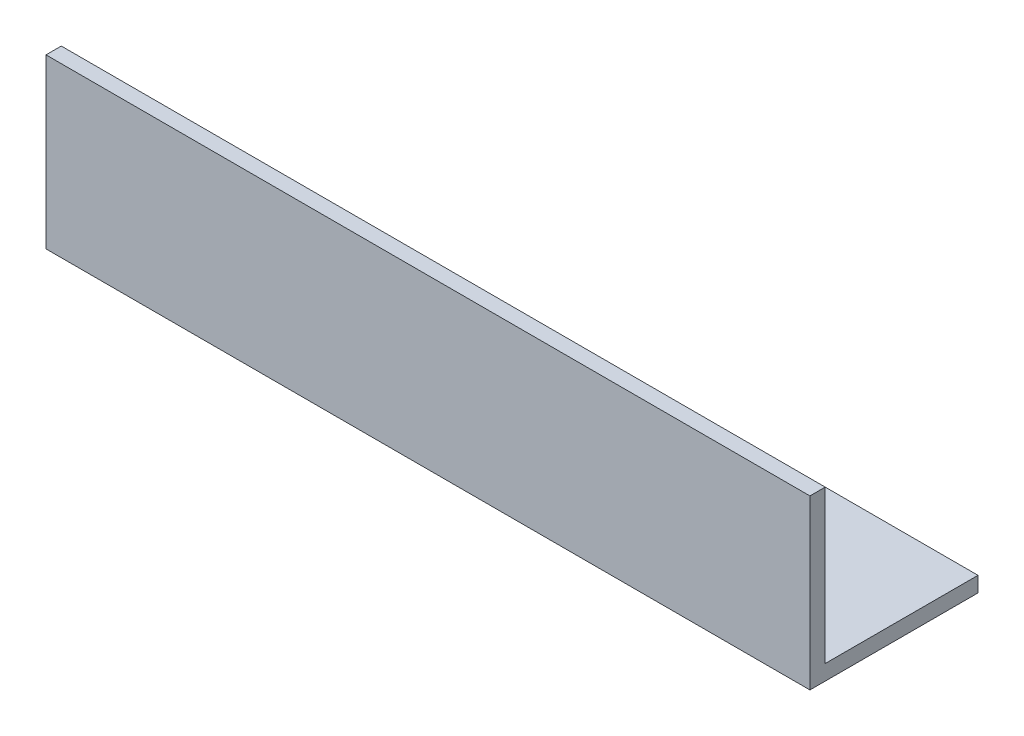
SolidWorks part; units mm, degrees
ref_plane "Спереди" through (0, 0, 0) normal (0, 0, 1) x (1, 0, 0)
ref_plane "Сверху" through (0, 0, 0) normal (0, 1, 0) x (1, 0, 0)
ref_plane "Справа" through (0, 0, 0) normal (1, 0, 0) x (0, 0, -1)
sketch "Эскиз1" plane through (0, 0, 0) normal (1, 0, 0) x (0, 0, -1)
  line L0 (0, 0) -> (0, 30)
  line L1 (0, 0) -> (30, 0)
extrude "Вытянуть-Тонкостенный1" add sketch "Эскиз1" along normal blind 150 thin thin type one direction wall 3
sketch "Эскиз2" plane through (0, -3, 0) normal (0, -1, 0) x (1, 0, 0)
  line L0 (75, -35.357) -> (75, 2.5686) construction
  circle A0 centre (130, -12) radius 5
  circle A1 centre (100, -12) radius 5
  circle A2 centre (50, -12) radius 5
  circle A3 centre (20, -12) radius 5
  dimension "D1" = 2
extrude "Вырез-Вытянуть1" cut sketch "Эскиз2" against normal through all
